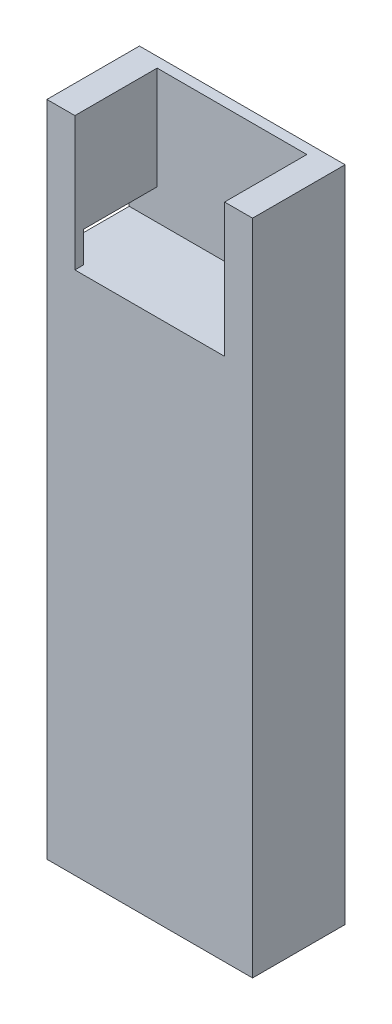
SolidWorks part; units mm, degrees
ref_plane "Front Plane" through (0, 0, 0) normal (0, 0, 1) x (1, 0, 0)
ref_plane "Top Plane" through (0, 0, 0) normal (0, 1, 0) x (1, 0, 0)
ref_plane "Right Plane" through (0, 0, 0) normal (1, 0, 0) x (0, 0, -1)
sketch "Sketch1" plane through (0, 0, 0) normal (0, 1, 0) x (1, 0, 0)
  line L1 (0, 0) -> (31.75, 0)
  line L2 (0, 0) -> (0, 14.2875)
  line L3 (0, 14.2875) -> (31.75, 14.2875)
  line L4 (31.75, 0) -> (31.75, 14.2875)
  dimension "D1" = 31.75
  dimension "D2" = 14.2875
extrude "Boss-Extrude1" add sketch "Sketch1" along normal blind 101.6
sketch "Sketch5" plane through (0, 101.6, 0) normal (0, 1, 0) x (1, 0, 0)
  line L0 (0, 0) -> (31.75, 0) construction
  line L1 (4.318, 0) -> (27.432, 0)
  line L2 (4.318, 0) -> (4.318, 12.7)
  line L3 (4.318, 12.7) -> (27.432, 12.7)
  line L4 (27.432, 0) -> (27.432, 12.7)
  line L8 (31.75, 14.2875) -> (0, 14.2875) construction
  point P11 (15.875, 14.2875)
  point P12 (15.875, 12.7)
  dimension "D1" = 12.7
  dimension "D2" = 23.114
  dimension "D3" = 0
extrude "Cut-Extrude2" cut sketch "Sketch5" against normal blind 20.6375
sketch "Sketch6" plane through (0, 0, 0) normal (-1, 0, 0) x (0, 0, 1)
  line L2 (-12.7, 80.9625) -> (-12.7, 85.725)
  line L5 (-12.7, 85.725) -> (-1.3543, 85.725)
  line L6 (-1.3543, 85.725) -> (-1.3543, 80.9625)
  line L7 (-1.3543, 80.9625) -> (-12.7, 80.9625)
  line L9 (0, 101.6) -> (0, 0) construction
  dimension "D1" = 4.7625
  dimension "D2" = 1.3543
extrude "Cut-Extrude4" cut sketch "Sketch6" against normal blind 9.2075
shell "Shell2" thickness 2.032 removed face at (15.875, 0, -7.1437)
